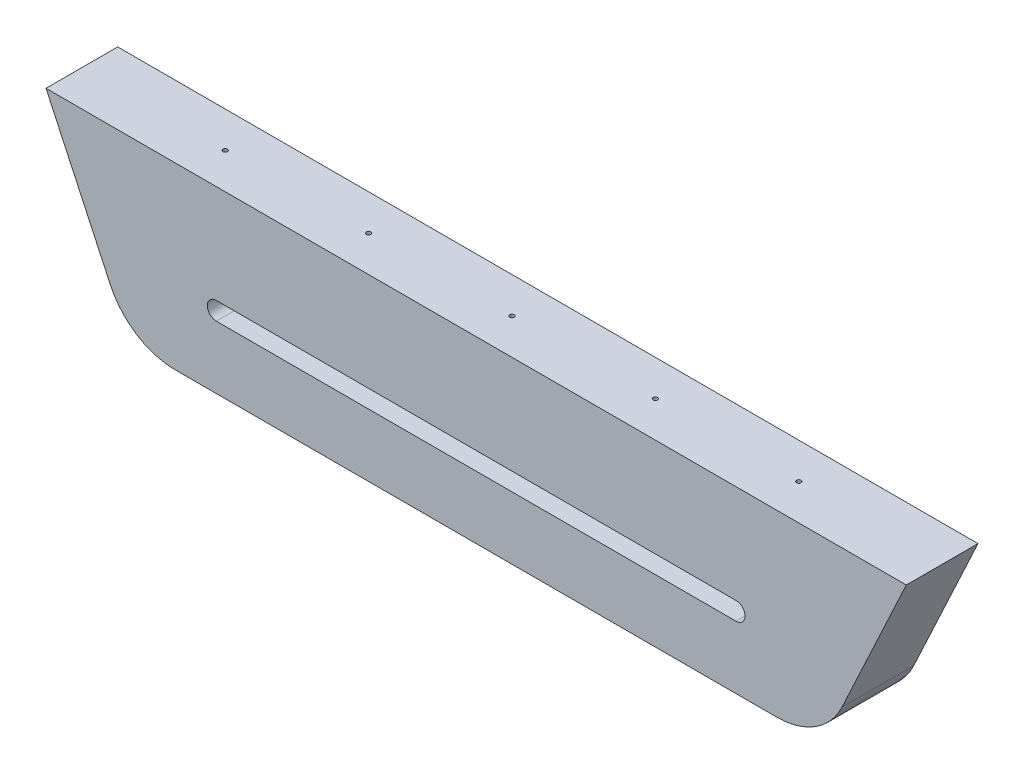
SolidWorks part; units mm, degrees
ref_plane "Front Plane" through (0, 0, 0) normal (0, 0, 1) x (1, 0, 0)
ref_plane "Top Plane" through (0, 0, 0) normal (0, 1, 0) x (1, 0, 0)
ref_plane "Right Plane" through (0, 0, 0) normal (1, 0, 0) x (0, 0, -1)
sketch "Sketch1" plane through (0, 0, 0) normal (0, 0, 1) x (1, 0, 0)
  line L0 (-152.4, 0) -> (152.4, 0)
  line L1 (152.4, 0) -> (122.7895, -63.5)
  line L2 (122.7895, -63.5) -> (-122.7895, -63.5)
  line L3 (-122.7895, -63.5) -> (-152.4, 0)
  line L4 (0, -63.5) -> (0, 0) construction
  dimension "D1" = 304.8
  dimension "D2" = 63.5
  dimension "D3" = 65
extrude "Boss-Extrude1" add sketch "Sketch1" along normal blind 25.4
fillet "Fillet1" radius 25.4 2 edges at (-122.7895, -63.5, 12.7) (122.7895, -63.5, 12.7)
hole_wizard "1/4 (0.25) Diameter Slot1" positions "Sketch2" profile "Sketch3" size "1/4" standard "ANSI Inch" slot yes end condition through all
sketch "Sketch2" plane through (0, 0, 25.4) normal (0, 0, 1) x (1, 0, 0)
  line L0 (-95.25, -38.1) -> (95.25, -38.1) construction
  line L1 (0, 0) -> (0, -38.1) construction
  line L2 (152.4, 0) -> (-152.4, 0) construction
  line L4 (0, -63.5) -> (0, -38.1) construction
  line L5 (-106.6079, -63.5) -> (106.6079, -63.5) construction
  point P0 (0, -38.1)
  dimension "D1" = 190.5
  dimension "D2" = 25.4
sketch "Sketch3" plane through (0, -38.1, 25.4) normal (1, 0, 0) x (0, -1, 0)
  line L0 (0, 0) -> (0, 25.4)
  line L1 (0, 25.4) -> (3.175, 25.4)
  line L2 (3.175, 25.4) -> (3.175, 0)
  line L5 (3.175, 0) -> (0, 0)
  line L11 (0, -6.35) -> (0, 107.95) construction
  dimension "Thru Hole Dia." = 6.35
  dimension "Thru Hole Depth" = 25.4
hole_wizard "1/16 (0.0625) Diameter Hole1" positions "Sketch4" profile "Sketch5" hole size "1/16" standard "ANSI Inch"
sketch "Sketch4" plane through (0, 0, 0) normal (0, 1, 0) x (1, 0, 0)
  line L0 (-152.4, -12.7) -> (-101.6, -12.7) construction
  line L1 (-152.4, -25.4) -> (-152.4, 0) construction
  point P0 (-101.6, -12.7)
  point P12 (-50.8, -12.7)
  point P13 (0, -12.7)
  point P14 (50.8, -12.7)
  point P15 (101.6, -12.7)
  dimension "D2" = 50.8
  dimension "D3" = 50.8
  dimension "D1" = 5
sketch "Sketch5" plane through (-101.6, 0, 12.7) normal (1, 0, 0) x (0, 0, 1)
  line L0 (0, 0) -> (0, 13.1769)
  line L1 (0, 13.1769) -> (0.7937, 12.7)
  line L2 (0.7937, 12.7) -> (0.7937, 0)
  line L5 (0.7937, 0) -> (0, 0)
  line L10 (0, 13.1769) -> (-0.7937, 12.7) construction
  line L11 (0, -6.35) -> (0, 107.95) construction
  dimension "Hole Dia." = 1.5875
  dimension "Hole Depth" = 12.7
  dimension "Drill Angle" = 118
